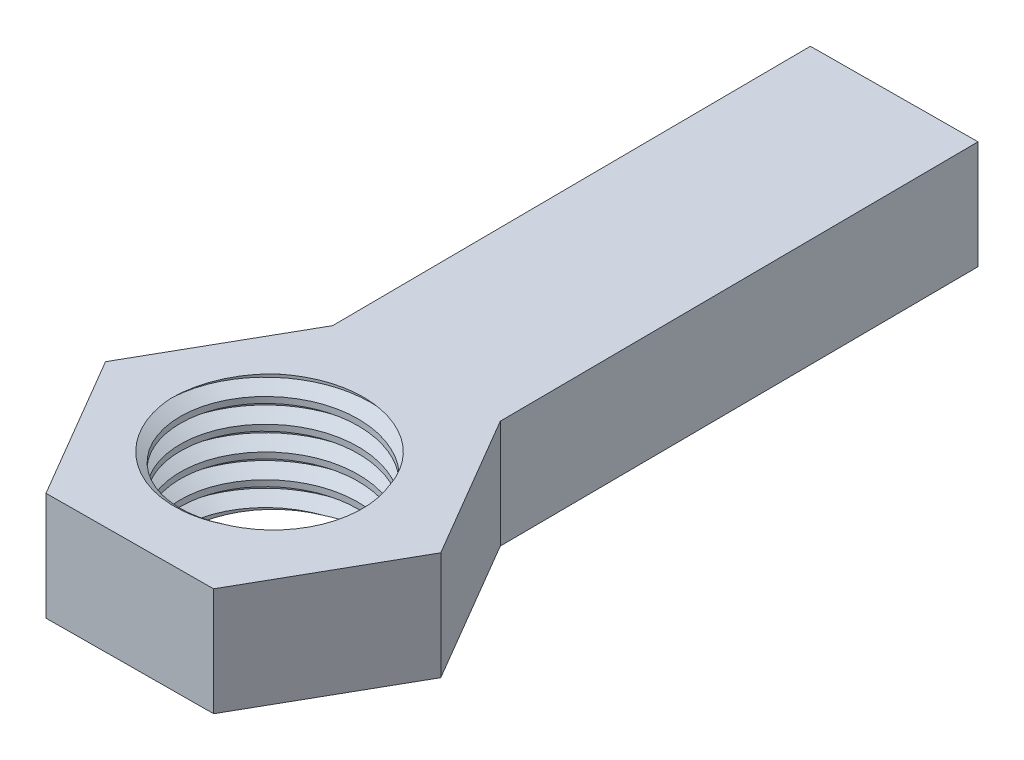
SolidWorks part; units mm, degrees
ref_plane "Front Plane" through (0, 0, 0) normal (0, 0, 1) x (1, 0, 0)
ref_plane "Top Plane" through (0, 0, 0) normal (0, 1, 0) x (1, 0, 0)
ref_plane "Right Plane" through (0, 0, 0) normal (1, 0, 0) x (0, 0, -1)
sketch "Sketch1" plane through (0, 0, 0) normal (0, 1, 0) x (1, 0, 0)
  line L1 (3.4254, 6.0222) -> (-3.5026, 5.9776)
  line L2 (-3.5026, 5.9776) -> (-6.9281, -0.0446)
  line L3 (-6.9281, -0.0446) -> (-3.4254, -6.0222)
  line L4 (-3.4254, -6.0222) -> (3.5026, -5.9776)
  line L5 (3.5026, -5.9776) -> (6.9281, 0.0446)
  line L6 (6.9281, 0.0446) -> (3.4254, 6.0222)
  circle A0 centre (0, 0) radius 6 construction
  dimension "D1" = 6
extrude "Boss-Extrude1" add sketch "Sketch1" along normal blind 4.5
sketch "Sketch2" plane through (0, 4.5, 0) normal (0, 1, 0) x (1, 0, 0)
  circle A0 centre (0, 0) radius 4.25
  dimension "D1" = 8.5
extrude "Cut-Extrude1" cut sketch "Sketch2" against normal through all
thread "Thread1" pitch 1 start angle 0, offset 1, length 62, pitch 1, diameter 8.5
ref_plane "Plane1" through (-4.25, 5.5, 0) normal (0, 0, 1) x (-1, 0, 0)
sketch "Thread Profile1" plane through (-4.25, 5.5, 0) normal (0, 0, 1) x (-1, 0, 0)
  line L0 (0, 0) -> (0, 1) construction
  line L11 (0, 0) -> (0, 0.875)
  line L12 (0, 0.875) -> (-0.5413, 0.5625)
  line L13 (-0.5413, 0.5625) -> (-0.5413, 0.3125)
  line L15 (-0.5413, 0.3125) -> (0, 0)
  line L17 (-0.5413, 0.4375) -> (0, 0.4375) construction
  point P2 (0, 0)
  dimension "Pitch" = 1
  dimension "Profile_Angle" = 60
  dimension "Profile_Land" = 0.25
  dimension "Profile_Height" = 0.5413
sketch "Sketch7" plane through (0, 4.5, 0) normal (0, 1, 0) x (1, 0, 0)
  circle A0 centre (0, 0) radius 6.4242
extrude "Cut-Extrude2" cut sketch "Sketch7" along normal blind 4
sketch "Sketch8" plane through (0, 0, 0) normal (0, -1, 0) x (1, 0, 0)
  circle A0 centre (0, 0) radius 7.3846
extrude "Cut-Extrude3" cut sketch "Sketch8" along normal through all
sketch "Sketch9" plane through (-0.0386, 0, -5.9999) normal (-0.0064, 0, -1) x (-1, 0, 0.0064)
  line L1 (-3.4641, 4.5) -> (3.4641, 4.5)
  line L2 (-3.4641, 4.5) -> (-3.4641, 0)
  line L3 (-3.4641, 0) -> (3.4641, 0)
  line L4 (3.4641, 4.5) -> (3.4641, 0)
extrude "Boss-Extrude2" add sketch "Sketch9" along normal blind 20
